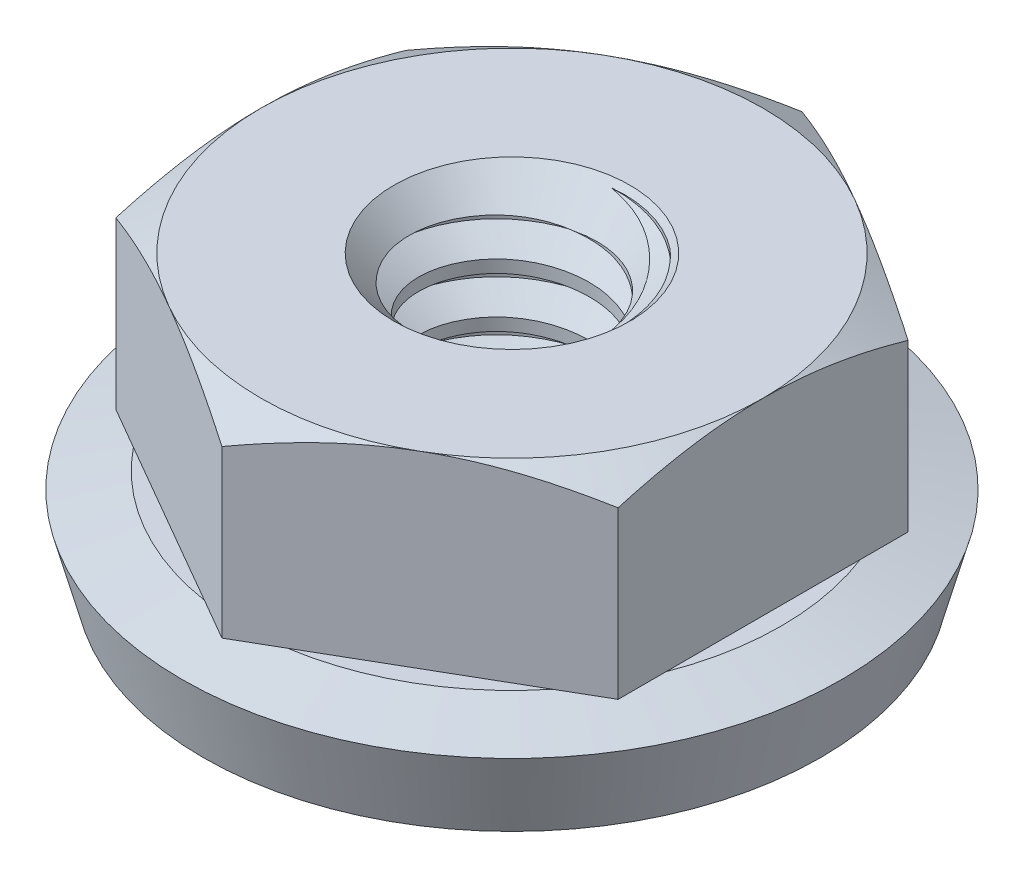
SolidWorks part; units mm, degrees
ref_plane "Front Plane" through (0, 0, 0) normal (0, 0, 1) x (1, 0, 0)
ref_plane "Top Plane" through (0, 0, 0) normal (0, 1, 0) x (1, 0, 0)
ref_plane "Right Plane" through (0, 0, 0) normal (1, 0, 0) x (0, 0, -1)
sketch "Sketch1" plane through (0, 0, 0) normal (0, 1, 0) x (1, 0, 0)
  line L1 (0, 3.6662) -> (-3.175, 1.8331)
  line L2 (-3.175, 1.8331) -> (-3.175, -1.8331)
  line L3 (-3.175, -1.8331) -> (0, -3.6662)
  line L4 (0, -3.6662) -> (3.175, -1.8331)
  line L5 (3.175, -1.8331) -> (3.175, 1.8331)
  line L6 (3.175, 1.8331) -> (0, 3.6662)
  circle A0 centre (0, 0) radius 3.175 construction
  circle A1 centre (0, 0) radius 4.1672 construction
  point P9 (0, 3.6662)
  point P10 (0, 4.1672)
  dimension "Wd." = 6.35
  dimension "Washer Dia." = 8.3344
extrude "Boss-Extrude1" add sketch "Sketch1" along normal blind 3.5719
sketch "Sketch4" plane through (0, 3.5719, 0) normal (0, 1, 0) x (1, 0, 0)
  circle A0 centre (0, 0) radius 1.4224
  dimension "Screw Dia." = 2.8448
sketch "Sketch5" plane through (0, 3.5719, 0) normal (0, 1, 0) x (1, 0, 0)
  circle A1 centre (0, 0) radius 1.4224
  circle A2 centre (0, 0) radius 1.4224
  point P0 (0, 1.4224)
  dimension "D1" = 0
curve "Helix/Spiral1" pitch 0.635 height 4.2069 turns 6.625 parameters "Pitch"=0.635
sketch "Sketch2" plane through (0, 3.5719, 0) normal (0, 1, 0) x (1, 0, 0)
  circle A0 centre (0, 0) radius 3.175 construction
  circle A1 centre (0, 0) radius 3.175
  point P3 (0, 3.175)
extrude "Cut-Extrude1" cut sketch "Sketch2" against normal through all draft 60 flip side to cut
sketch "Sketch3" plane through (0, 0, 0) normal (0, -1, 0) x (1, 0, 0)
  circle A1 centre (0, 0) radius 3.175
  circle A2 centre (0, 0) radius 3.175
  dimension "D1" = 0
extrude "Cut-Extrude2" [suppressed] cut sketch "Sketch3" against normal through all draft 60 flip side to cut
extrude "Cut-Extrude3" cut sketch "Sketch4" against normal up to vertex (3.5719 mm away) up to point (0, 0, 0)
sketch "Sketch6" plane through (0, 0, 0) normal (1, 0, 0) x (0, 0, -1)
  line L0 (1.4911, 4.1672) -> (1.4911, 3.5322) construction
  line L1 (1.4911, 3.5322) -> (0.9412, 3.8497) construction
  line L2 (0.9412, 3.8497) -> (1.4911, 4.1672) construction
  line L3 (1.01, 3.8894) -> (1.01, 3.81) construction
  line L4 (0.9412, 3.8497) -> (1.01, 3.8497) construction
  line L5 (1.4224, 4.1275) -> (1.4224, 3.5719) construction
  line L6 (1.4224, 3.8497) -> (1.4911, 3.8497) construction
  line L7 (1.4568, 4.1473) -> (1.0787, 3.9291)
  line L8 (1.0787, 3.9291) -> (1.0787, 3.7703)
  line L9 (1.0787, 3.7703) -> (1.4568, 3.552)
  line L10 (1.4568, 3.552) -> (1.4568, 4.1473)
  line L11 (1.01, 3.8497) -> (1.0787, 3.8497) construction
  point P13 (1.4568, 3.8497)
  dimension "D1" = 0.635
  dimension "D2" = 0.0794
sweep "Sweep1" add profiles "Sketch6" path "Helix/Spiral1"
sketch "Sketch7" plane through (0, 3.5719, 0) normal (0, 1, 0) x (1, 0, 0)
  line L0 (-1.4911, 0) -> (0, 0) construction
  circle A0 centre (0, 0) radius 1.4911
extrude "Cut-Extrude4" cut sketch "Sketch7" against normal through all draft 45 and the other way through all draft 45
sketch "Sketch8" plane through (0, 0, 0) normal (0, -1, 0) x (1, 0, 0)
  circle A1 centre (0, 0) radius 1.4911
  circle A2 centre (0, 0) radius 1.4911
  dimension "D1" = 0
extrude "Cut-Extrude5" cut sketch "Sketch8" against normal through all draft 45 and the other way through all draft 45
sketch "Sketch9" plane through (0, 0, 0) normal (1, 0, 0) x (0, 0, -1)
  line L0 (4.1672, 0) -> (-4.1672, 0) construction
  line L1 (2.613, 0) -> (3.6662, 0)
  line L2 (0, 0) -> (0, 1.1906) construction
  line L3 (2.613, 1.1906) -> (3.6662, 1.1906)
  line L4 (3.6662, 0) -> (3.6662, 1.1906)
  line L5 (0, 1.1906) -> (0, 3.5719) construction
  line L6 (2.613, 1.1906) -> (2.613, 0)
  line L7 (1.4224, 3.5719) -> (1.4224, 1.1906) construction
  line L8 (1.4224, 1.1906) -> (2.613, 1.1906) construction
  dimension "D" = 2.3813
revolve "Cut-Revolve1" cut sketch "Sketch9" angle 360 mid plane about L2
sketch "Sketch10" plane through (0, 0, 0) normal (1, 0, 0) x (0, 0, -1)
  line L0 (2.613, 1.1906) -> (2.613, 0) construction
  line L1 (2.613, 1.1906) -> (3.4036, 1.1906)
  line L2 (2.613, 1.1906) -> (2.613, 0.2046)
  line L3 (2.613, 0.2046) -> (3.1394, 0.2046)
  line L4 (4.1672, 0.986) -> (3.903, 0)
  line L5 (0, 1.1906) -> (0, 0) construction
  line L6 (4.1672, 0.986) -> (3.4036, 1.1906)
  line L7 (3.903, 0) -> (3.1394, 0.2046)
  line L8 (3.1394, 0.2046) -> (3.4036, 1.1906) construction
  line L9 (2.613, 0) -> (3.6662, 0) construction
  dimension "D1" = 165
revolve "Revolve1" add sketch "Sketch10" angle 360 mid plane about L5
equation "\"D3@Helix/Spiral1\" = \"Pitch@Helix/Spiral1\" + \"Ht.@Boss-Extrude1\""
equation "\"D1@Sketch6\" = \"Pitch@Helix/Spiral1\""
equation "\"D2@Sketch6\" = \"D1@Sketch6\" / 8"
